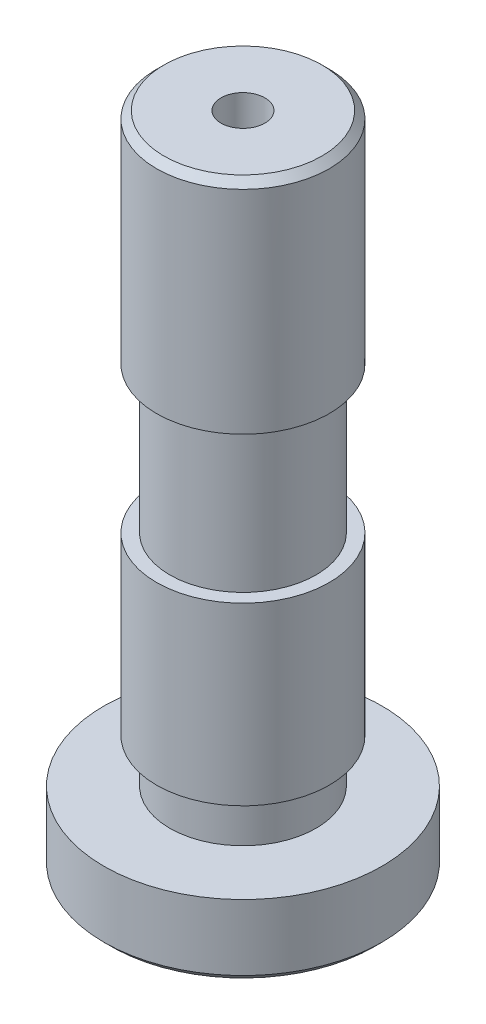
SolidWorks part; units mm, degrees
material "AISI 1020 Сталь, холоднокатаная"
ref_plane "Спереди" through (0, 0, 0) normal (0, 0, 1) x (1, 0, 0)
ref_plane "Сверху" through (0, 0, 0) normal (0, 1, 0) x (1, 0, 0)
ref_plane "Справа" through (0, 0, 0) normal (1, 0, 0) x (0, 0, -1)
sketch "Эскиз1" plane through (0, 0, 0) normal (0, 0, 1) x (1, 0, 0)
  line L0 (0, 14.6468) -> (0, -10.5782) construction
  line L1 (0, 0) -> (9.5, 0)
  line L2 (9.5, 0) -> (9.5, 5)
  line L3 (9.5, 5) -> (5, 5)
  line L4 (5, 5) -> (5, 8)
  line L5 (5, 8) -> (5.9, 8)
  line L6 (5.9, 8) -> (5.9, 20)
  line L7 (5.9, 20) -> (5, 20)
  line L9 (5.9, 45) -> (0, 45)
  line L10 (0, 45) -> (0, 0)
  line L11 (5, 20) -> (5, 30)
  line L12 (5, 30) -> (5.9, 30)
  line L13 (5.9, 30) -> (5.9, 45)
  line L14 (5, 25) -> (-6.4103, 25) construction
  dimension "D1" = 19
  dimension "D2" = 5
  dimension "D3" = 3
  dimension "D4" = 45
  dimension "D5" = 15
  dimension "D6" = 12
  dimension "D7" = 11.8
  dimension "D8" = 10
revolve "Повернуть1" add sketch "Эскиз1" angle 360 about L0
sketch "Эскиз2" plane through (0, 45, 0) normal (0, 1, 0) x (1, 0, 0)
  circle A0 centre (0, 0) radius 1.5
  dimension "D1" = 3
extrude "Вырез-Вытянуть1" cut sketch "Эскиз2" against normal blind 3
sketch "Эскиз3" plane through (0, 0, 0) normal (0, -1, 0) x (-1, 0, 0)
  circle A0 centre (0, 0) radius 1.5
  dimension "D1" = 3
extrude "Вырез-Вытянуть2" cut sketch "Эскиз3" against normal blind 3
chamfer "Фаска1" distance 0.5 angle 45 2 edges at (0, 0, 9.5) (0, 45, 5.9)
